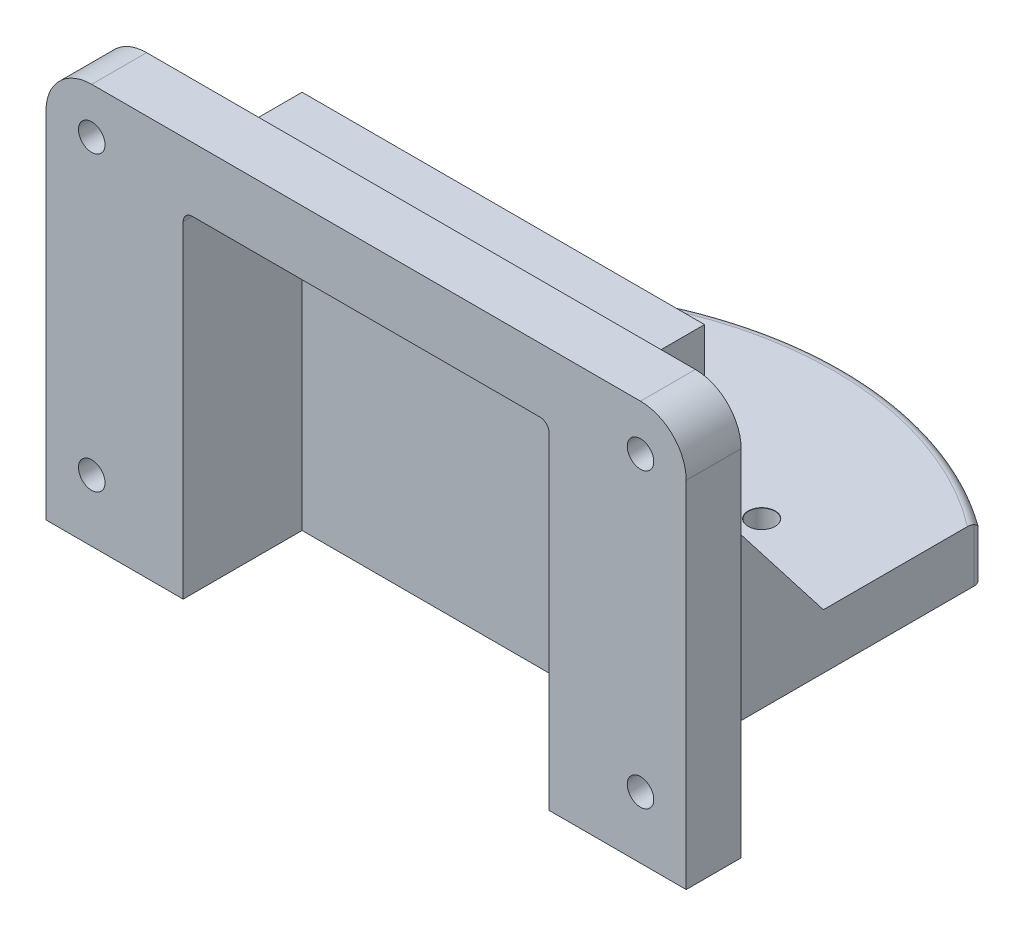
SolidWorks part; units mm, degrees
ref_plane "前视基准面" through (0, 0, 0) normal (0, 0, 1) x (1, 0, 0)
ref_plane "上视基准面" through (0, 0, 0) normal (0, 1, 0) x (1, 0, 0)
ref_plane "右视基准面" through (0, 0, 0) normal (1, 0, 0) x (0, 0, -1)
sketch "草图1" plane through (0, 0, 0) normal (0, 0, 1) x (1, 0, 0)
  line L0 (0, 0) -> (16, 0) construction
  line L1 (0, 0) -> (-28, 0) construction
  line L2 (0, 0) -> (0, -38.75) construction
  line L3 (0, -38.75) -> (-28, -38.75) construction
  line L4 (-28, 0) -> (-28, -38.75) construction
  line L5 (-14, 0) -> (-14, -28.75) construction
  line L6 (-49, 5) -> (-49, -38.75)
  line L8 (-49, 5) -> (21, 5)
  line L9 (21, 5) -> (21, -38.75)
  line L10 (21, -38.75) -> (-49, -38.75)
  point P10 (-14, -38.75)
  point P15 (-14, 5)
  dimension "D1" = 28
  dimension "D2" = 38.75
  dimension "D3" = 16
  dimension "D4" = 5
  dimension "D5" = 5
extrude "凸台-拉伸1" add sketch "草图1" along normal blind 6
sketch "草图2" plane through (0, 0, 6) normal (0, 0, 1) x (1, 0, 0)
  line L0 (-14, 5) -> (-14, -28.75) construction
  line L5 (-13.9078, 0.75) -> (8, 0.75)
  line L6 (8, 0.75) -> (8, -38.75)
  line L7 (-49, -38.75) -> (21, -38.75) construction
  line L8 (8, -38.75) -> (-36, -38.75)
  line L10 (-36, 0.75) -> (-36, -38.75)
  line L11 (-13.9078, 0.75) -> (-36, 0.75)
  point P11 (-14, -38.75)
  point P14 (-14, 19.75)
  dimension "D3" = 22
  dimension "D4" = 39.5
extrude "凸台-拉伸2" add sketch "草图2" against normal blind 15
sketch "草图3" plane through (0, 0, 6) normal (0, 0, 1) x (1, 0, 0)
  line L0 (-14, 19.75) -> (-14, -38.75) construction
  line L5 (-14, -2) -> (6, -2)
  line L6 (6, -2) -> (6, -38.75)
  line L7 (-49, -38.75) -> (21, -38.75) construction
  line L8 (6, -38.75) -> (-34, -38.75)
  line L9 (21, 5) -> (-49, 5) construction
  line L11 (-34, -2) -> (-34, -38.75)
  line L12 (-14, -2) -> (-34, -2)
  point P15 (-14, -38.75)
  dimension "D2" = 7
  dimension "D3" = 20
extrude "切除-拉伸1" cut sketch "草图3" against normal blind 13
sketch "草图5" plane through (0, -38.75, 0) normal (0, -1, 0) x (1, 0, 0)
  line L0 (-36, -9) -> (-36, -39)
  line L1 (-36, -9) -> (8, -9) construction
  line L2 (8, -39) -> (8, -9)
  line L3 (-36, -9) -> (8, -9)
  arc A0 (-36, -39) -> (8, -39) centre (-14, -9) ccw
  dimension "D1" = 30
extrude "凸台-拉伸4" add sketch "草图5" against normal blind 6 contours L3 L2 A0 L0
sketch "草图12" plane through (8, 0, 0) normal (1, 0, 0) x (0, 0, -1)
  line L0 (9, -32.75) -> (22, -32.75)
  line L1 (39, -32.75) -> (9, -32.75) construction
  line L2 (22, -32.75) -> (9, -16)
  line L3 (9, -32.75) -> (9, 0.75) construction
  line L4 (9, -16) -> (9, -32.75)
  dimension "D1" = 13
extrude "凸台-拉伸5" add sketch "草图12" against normal up to surface (44 mm away) up to face at (-36, -23.5833, -16)
fillet "圆角3" radius 1 3 edges at (-36, -35.75, -39) (-14, -32.75, -46.2022) (8, -35.75, -39)
fillet "圆角5" radius 4 2 edges at (-36, -19, 0) (8, -19, 0)
fillet "圆角6" radius 1 2 edges at (6, -2, -0.5) (-34, -2, -0.5)
fillet "圆角7" radius 5 2 edges at (-49, 5, 3) (21, 5, 3)
hole_wizard "M2.5 间隙孔1" positions "草图6" profile "草图7" hole size "M2.5" standard "ISO" end condition through all
sketch "草图6" plane through (0, 0, 0) normal (0, 0, -1) x (-1, 0, 0)
  line L0 (14, 19.75) -> (14, -38.75) construction
  line L1 (-12, -38.75) -> (-21, -38.75) construction
  point P0 (-16, 0)
  point P11 (-16, -32)
  point P18 (44, -32)
  point P19 (44, 0)
  dimension "D1" = 30
  dimension "D2" = 30
  dimension "D3" = 6.75
  dimension "D4" = 32
sketch "草图7" plane through (16, 0, 0) normal (1, 0, 0) x (0, 1, 0)
  line L0 (0, 0) -> (0, 6)
  line L1 (0, 6) -> (1.45, 6)
  line L2 (1.45, 6) -> (1.45, 0.025)
  line L3 (1.45, 0.025) -> (1.475, 0)
  line L5 (1.475, 0) -> (0, 0)
  line L6 (-1.45, 0.025) -> (-1.475, 0) construction
  line L11 (0, -6.35) -> (0, 107.95) construction
  dimension "通孔孔直径" = 2.9
  dimension "通孔孔深度" = 6
  dimension "近端锥形沉头孔直径" = 2.95
  dimension "近端锥形沉头孔角度" = 90
hole_wizard "M2.5 间隙孔3" positions "草图10" profile "草图11" hole size "M2.5" standard "ISO" end condition through all
sketch "草图10" plane through (0, -32.75, 0) normal (0, 1, 0) x (1, 0, 0)
  line L0 (-14, 8) -> (-14, 40.755) construction
  line L3 (-15.1601, -22.75) -> (69.9162, -22.75) construction
  line L4 (16, -6) -> (-44, -6) construction
  point P0 (-24, 27.25)
  point P21 (-4, 27.25)
  dimension "D1" = 10
  dimension "D2" = 50
  dimension "D3" = 16.75
sketch "草图11" plane through (-24, -32.75, -27.25) normal (1, 0, 0) x (0, 0, 1)
  line L0 (0, 0) -> (0, 6)
  line L1 (0, 6) -> (1.45, 6)
  line L2 (1.45, 6) -> (1.45, 0.025)
  line L3 (1.45, 0.025) -> (1.475, 0)
  line L5 (1.475, 0) -> (0, 0)
  line L6 (-1.45, 0.025) -> (-1.475, 0) construction
  line L11 (0, -6.35) -> (0, 107.95) construction
  dimension "通孔孔直径" = 2.9
  dimension "通孔孔深度" = 6
  dimension "近端锥形沉头孔直径" = 2.95
  dimension "近端锥形沉头孔角度" = 90
